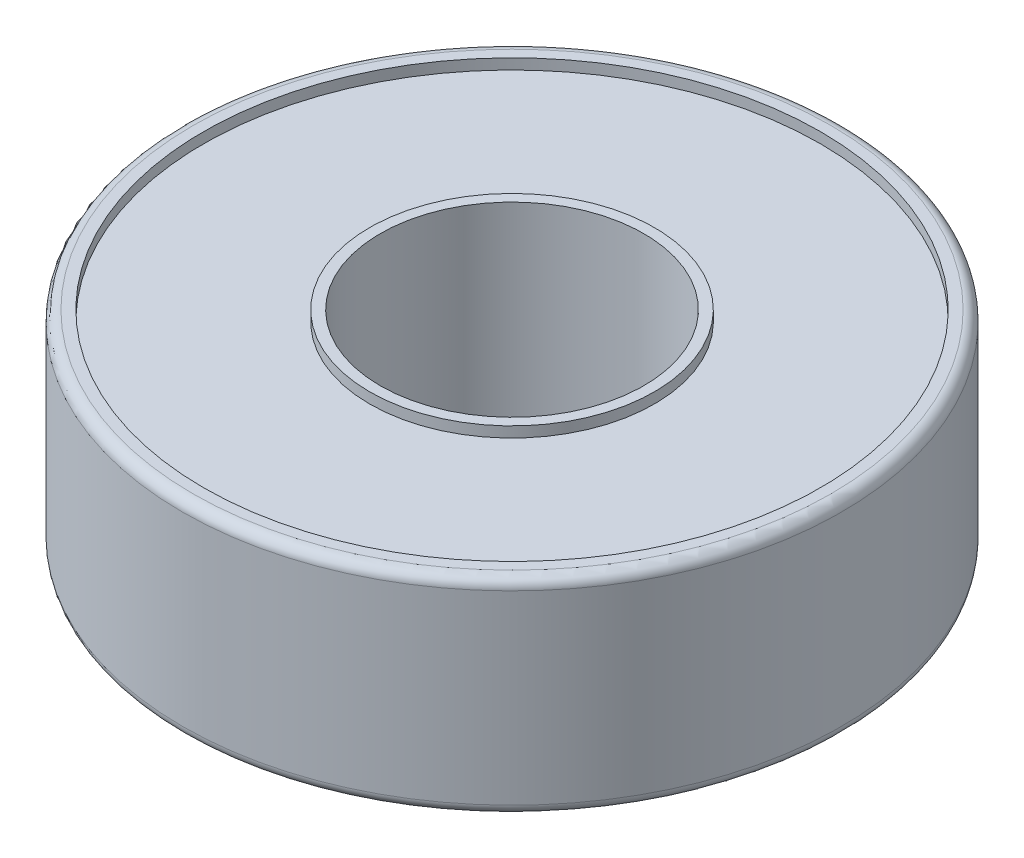
SolidWorks part; units mm, degrees
ref_plane "Front Plane" through (0, 0, 0) normal (0, 0, 1) x (1, 0, 0)
ref_plane "Top Plane" through (0, 0, 0) normal (0, 1, 0) x (1, 0, 0)
ref_plane "Right Plane" through (0, 0, 0) normal (1, 0, 0) x (0, 0, -1)
sketch "Sketch1" plane through (0, 0, 0) normal (0, 1, 0) x (1, 0, 0)
  circle A0 centre (0, 0) radius 7.9375
  circle A1 centre (0, 0) radius 3.175
  dimension "D1" = 15.875
  dimension "D2" = 6.35
extrude "Boss-Extrude1" add sketch "Sketch1" along normal blind 2.4892 and the other way blind 2.4892
fillet "Fillet1" radius 0.254 2 edges at (0, -2.4892, 7.9375) (0, 2.4892, 7.9375)
sketch "Sketch2" plane through (0, 2.4892, 0) normal (0, 1, 0) x (1, 0, 0)
  circle A0 centre (0, 0) radius 3.175 construction
  circle A1 centre (0, 0) radius 3.175 construction
  circle A2 centre (0, 0) radius 3.429
  circle A3 centre (0, 0) radius 7.6835 construction
  circle A4 centre (0, 0) radius 7.6835 construction
  circle A5 centre (0, 0) radius 7.4295
  dimension "D1" = 0.254
  dimension "D2" = 0.254
extrude "Cut-Extrude1" cut sketch "Sketch2" against normal blind 0.254
mirror "Mirror1" about plane through (0, 0, 0) normal (0, 1, 0) of "Cut-Extrude1"
